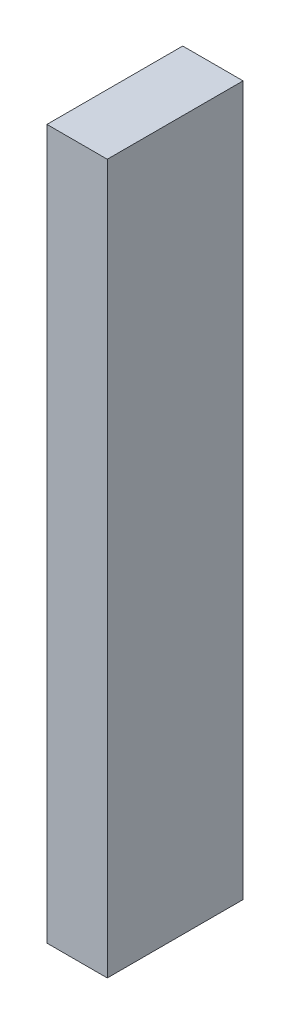
SolidWorks part; units mm, degrees
material "MDF"
ref_plane "Front Plane" through (0, 0, 0) normal (0, 0, 1) x (1, 0, 0)
ref_plane "Top Plane" through (0, 0, 0) normal (0, 1, 0) x (1, 0, 0)
ref_plane "Right Plane" through (0, 0, 0) normal (1, 0, 0) x (0, 0, -1)
sketch "Sketch1" plane through (0, 0, 0) normal (0, 0, 1) x (1, 0, 0)
  line L1 (-126.4888, -460.375) -> (-113.7888, -460.375)
  line L2 (-126.4888, -460.375) -> (-126.4888, -311.15)
  line L3 (-126.4888, -311.15) -> (-113.7888, -311.15)
  line L4 (-113.7888, -460.375) -> (-113.7888, -311.15)
  point P4 (0, 0)
  dimension "D1" = 12.7
  dimension "D3" = 149.225
extrude "Boss-Extrude1" add sketch "Sketch1" along normal blind 28.575
hole_wizard "Hole1" positions "Sketch2" profile "Sketch3" legacy
sketch "Sketch2" plane through (0, 0, -25.4) normal (0, 0, -1) x (-1, 0, 0)
  line L0 (218.5638, 0) -> (218.5638, -437.642) construction
  line L4 (104.2638, 0) -> (104.2638, -298.45) construction
  line L13 (120.1388, -460.375) -> (120.1388, -311.15) construction
  line L16 (126.4888, -311.15) -> (113.7888, -311.15) construction
  line L18 (126.4888, -304.8) -> (-126.4888, -304.8) construction
  line L22 (94.7388, -276.225) -> (-94.7388, -276.225) construction
  line L24 (-94.7388, -285.75) -> (-94.7388, -266.7) construction
  line L26 (94.7388, -285.75) -> (94.7388, -266.7) construction
  line L27 (-94.7388, 0) -> (-94.7388, -19.05) construction
  line L29 (94.7388, 0) -> (94.7388, -19.05) construction
  line L31 (94.7388, -9.525) -> (-94.7388, -9.525) construction
  point P15 (218.5638, -31.75)
  point P17 (218.5638, -218.821)
  point P19 (218.5638, -418.592)
  point P28 (104.2638, -19.05)
  point P30 (104.2638, -149.225)
  point P32 (104.2638, -279.4)
  point P69 (120.1388, -330.2)
  point P71 (120.1388, -441.325)
  point P76 (-120.1388, -441.325)
  point P77 (-120.1388, -330.2)
  point P80 (-104.2638, -279.4)
  point P81 (-104.2638, -149.225)
  point P82 (-104.2638, -19.05)
  point P83 (-218.5638, -418.592)
  point P84 (-218.5638, -218.821)
  point P85 (-218.5638, -31.75)
  point P99 (0, -304.8)
  point P101 (107.4388, -304.8)
  point P103 (-107.4388, -304.8)
  point P127 (75.6888, -276.225)
  point P129 (0, -276.225)
  point P131 (-75.6888, -276.225)
  point P152 (75.6888, -9.525)
  point P154 (0, -9.525)
  point P156 (-75.6888, -9.525)
  point P158 (0, 0)
sketch "Sketch3" plane through (75.6888, -9.525, -25.4) normal (1, 0, 0) x (0, 1, 0)
  line L0 (0, 0) -> (0, 39.0539)
  line L1 (0, 39.0539) -> (1.5875, 38.1)
  line L2 (1.5875, 38.1) -> (1.5875, 4.0177)
  line L3 (1.5875, 4.0177) -> (5.08, 0)
  line L4 (5.08, 0) -> (0, 0)
  line L5 (0, -14.3089) -> (0, 102.4216) construction
  line L6 (0, 39.0539) -> (-1.5875, 38.1) construction
  line L7 (-1.5875, 4.0177) -> (-5.08, 0) construction
  dimension "Diameter" = 3.175
  dimension "Depth" = 38.1
  dimension "C-Sink Diameter" = 10.16
  dimension "C-Sink Angle" = 82
  dimension "Drill Angle" = 118
